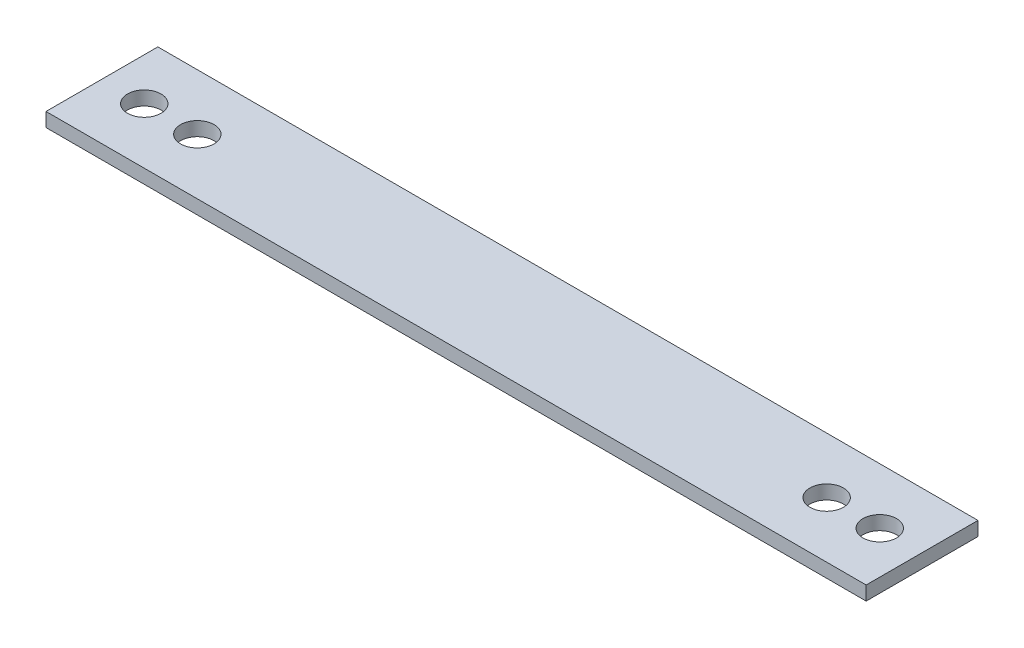
SolidWorks part; units mm, degrees
ref_plane "Front Plane" through (0, 0, 0) normal (0, 0, 1) x (1, 0, 0)
ref_plane "Top Plane" through (0, 0, 0) normal (0, 1, 0) x (1, 0, 0)
ref_plane "Right Plane" through (0, 0, 0) normal (1, 0, 0) x (0, 0, -1)
sketch "Sketch2" plane through (0, 0, 0) normal (0, 1, 0) x (1, 0, 0)
  line L1 (-139.7, -19.05) -> (139.7, -19.05)
  line L2 (-139.7, -19.05) -> (-139.7, 19.05)
  line L3 (-139.7, 19.05) -> (139.7, 19.05)
  line L4 (139.7, -19.05) -> (139.7, 19.05)
  line L5 (0, 19.05) -> (0, -19.05) construction
  line L6 (-139.7, 0) -> (139.7, 0) construction
  circle A0 centre (-125.278, 0) radius 5.7124
  circle A1 centre (-107.1966, 0) radius 5.7124
  circle A2 centre (125.278, 0) radius 5.7124
  circle A3 centre (107.1966, 0) radius 5.7124
  point P0 (0, 0)
  dimension "D1" = 38.1
  dimension "D2" = 279.4
extrude "Boss-Extrude1" add sketch "Sketch2" along normal blind 4.7625
